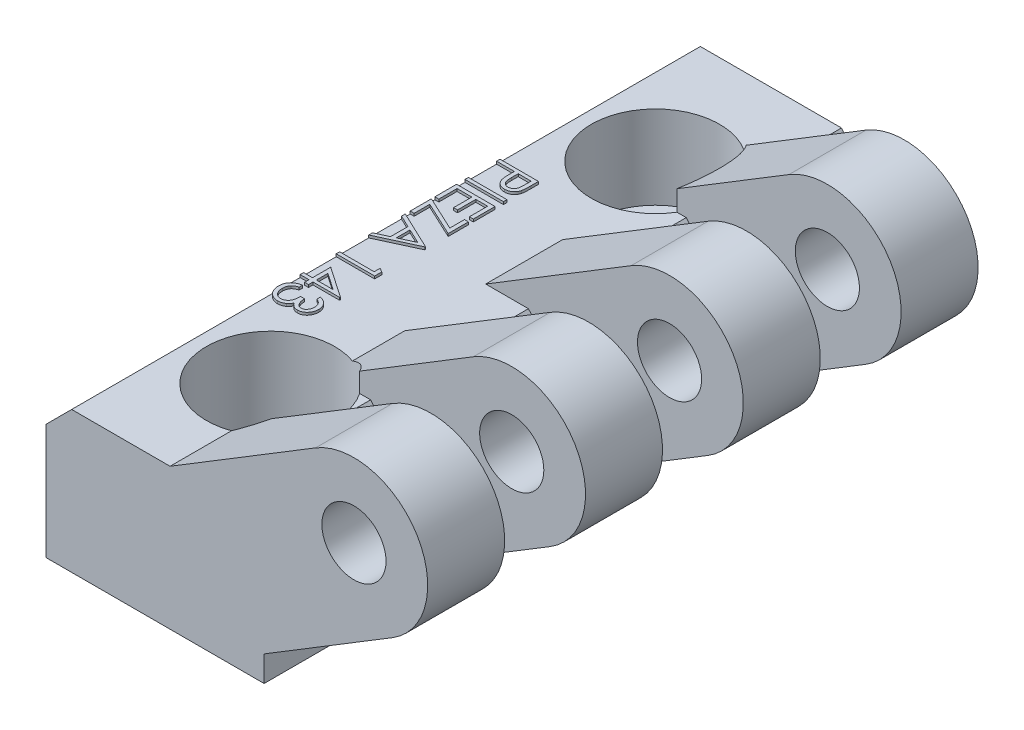
SolidWorks part; units mm, degrees
material "PVC Rígido"
ref_plane "Alzado" through (0, 0, 0) normal (0, 0, 1) x (1, 0, 0)
ref_plane "Planta" through (0, 0, 0) normal (0, 1, 0) x (1, 0, 0)
ref_plane "Vista lateral" through (0, 0, 0) normal (1, 0, 0) x (0, 0, -1)
sketch "Croquis2" plane through (0, 0, 0) normal (0, 0, 1) x (1, 0, 0)
  line L7 (-24, -13) -> (-7, -13)
  line L8 (-24, -13) -> (-24, -4)
  line L9 (-22, -2) -> (-11, -2)
  line L10 (-7, -11) -> (-4.4383, -9.4387)
  line L12 (-24, -4) -> (-22, -2)
  line L13 (-7, -13) -> (-7, -11)
  line L14 (-11, -2) -> (-4.4383, -9.4387)
  circle A3 centre (0, 0) radius 2.5 construction
  dimension "D2" = 13
  dimension "D3" = 19.5617
  dimension "D14" = 5
  dimension "D4" = 24
  dimension "D5" = 11
  dimension "D13" = 17
  dimension "D15" = 2
  dimension "D16" = 2
  dimension "D17" = 2
  dimension "D18" = 3
  dimension "D19" = 13
extrude "Saliente-Extruir1" add sketch "Croquis2" along normal mid plane 49
sketch "Croquis11" plane through (0, 0, 24.5) normal (0, 0, 1) x (1, 0, 0)
  line L0 (-11, -2) -> (-22, -2) construction
  line L2 (-14.3302, -2) -> (-11, -2)
  line L3 (-4.4383, -9.4387) -> (2.9924, -4.91)
  line L4 (-2.9924, 4.91) -> (-14.3302, -2)
  line L7 (-11, -2) -> (-4.4383, -9.4387)
  arc A0 (2.9924, -4.91) -> (-2.9924, 4.91) centre (0, 0) ccw
  circle A1 centre (0, 0) radius 2.5
  dimension "D1" = 11.5
  dimension "D5" = 5
extrude "Saliente-Extruir4" add sketch "Croquis11" against normal blind 6
pattern_linear "MatrizL1" count 4 spacing 12.3 along (0, 0, -1) of "Saliente-Extruir4"
sketch "Croquis12" plane through (0, -13, 0) normal (0, -1, 0) x (1, 0, 0)
  line L0 (-24, -24.5) -> (-7, -24.5) construction
  line L1 (-24, 24.5) -> (-24, -24.5) construction
  circle A0 centre (-16, -15) radius 2.75
  circle A1 centre (-16, 15) radius 2.75
  dimension "D1" = 30
  dimension "D2" = 9.5
  dimension "D3" = 8
  dimension "D4" = 5.5
extrude "Cortar-Extruir3" cut sketch "Croquis12" against normal through all
sketch "Croquis13" plane through (0, -2, 0) normal (0, 1, 0) x (1, 0, 0)
  circle A0 centre (-16, 15) radius 5
  circle A1 centre (-16, -15) radius 5
  dimension "D1" = 10
extrude "Cortar-Extruir4" cut sketch "Croquis13" against normal blind 6.5 and the other way blind 6.5
sketch "Croquis14" plane through (-24, 0, 0) normal (-1, 0, 0) x (0, 0, 1)
  text T0 "PIAZ LT-1I-BIS303002" font "Century Gothic" height 2.5
extrude "Saliente-Extruir5" add sketch "Croquis14" along normal blind 0.2
sketch "Croquis15" plane through (0, -2, 0) normal (0, 1, 0) x (1, 0, 0)
  text T0 "PIEZA 143             " font "Century Gothic" height 3
extrude "Saliente-Extruir6" add sketch "Croquis15" along normal blind 0.2
